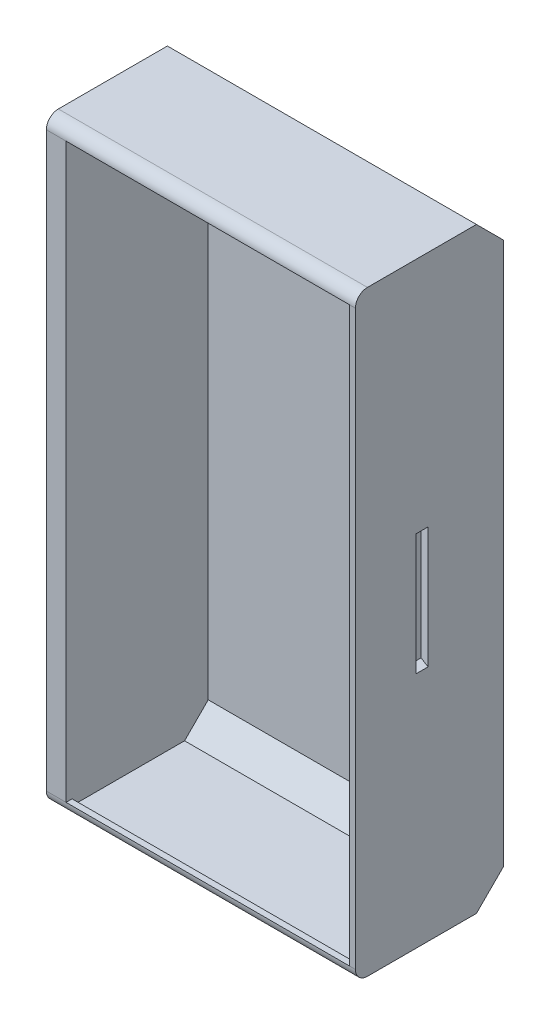
SolidWorks part; units mm, degrees
ref_plane "Front Plane" through (0, 0, 0) normal (1, 0, 0) x (0, 1, 0)
ref_plane "Top Plane" through (0, 0, 0) normal (0, 0, 1) x (0, 1, 0)
ref_plane "Right Plane" through (0, 0, 0) normal (0, 1, 0) x (-1, 0, 0)
sketch "Sketch1" plane through (0, 0, 0) normal (1, 0, 0) x (0, 1, 0)
  line L12 (-98.46, -46.9834) -> (-89.4834, -55.96)
  line L13 (-89.4834, -55.96) -> (89.4834, -55.96)
  line L14 (89.4834, -55.96) -> (98.46, -46.9834)
  line L15 (98.46, -46.9834) -> (98.46, -11)
  line L16 (94.5, -7.04) -> (-94.5, -7.04)
  line L17 (-98.46, -11) -> (-98.46, -46.9834)
  line L18 (-98.46, -46.9834) -> (-89.4834, -55.96)
  line L19 (-89.4834, -55.96) -> (89.4834, -55.96)
  line L20 (89.4834, -55.96) -> (98.46, -46.9834)
  line L21 (98.46, -46.9834) -> (98.46, -11)
  line L22 (94.5, -7.04) -> (-94.5, -7.04)
  line L23 (-98.46, -11) -> (-98.46, -46.9834)
  arc A4 (98.46, -11) -> (94.5, -7.04) centre (94.5, -11) ccw
  arc A5 (-94.5, -7.04) -> (-98.46, -11) centre (-94.5, -11) ccw
  arc A6 (98.46, -11) -> (94.5, -7.04) centre (94.5, -11) ccw
  arc A7 (-94.5, -7.04) -> (-98.46, -11) centre (-94.5, -11) ccw
  dimension "D1" = 0.04
extrude "Boss-Extrude1" add sketch "Sketch1" along normal up to surface (102 mm away) contours L18 L19 L20 L21 A6 L22 A7 L23
ref_plane "Plane3" through (0, 0, 0) normal (0, 1, 0) x (1, 0, 0)
sketch "Sketch11" plane through (0, 0, 0) normal (0, 1, 0) x (1, 0, 0)
  line L0 (102, 28.9917) -> (105.7243, 27.5325)
  line L1 (102, 11) -> (102, 46.9834) construction
  line L2 (102, 28.9917) -> (98.2757, 30.451)
  dimension "D1" = 4
  dimension "D2" = 4
sketch "Sketch12" plane through (102, 0, 0) normal (1, 0, 0) x (0, 1, 0)
  line L0 (0, -28.9917) -> (0, -27.5325) construction
  line L1 (-20, -30.9917) -> (20, -30.9917)
  line L2 (-20, -30.9917) -> (-20, -26.9917)
  line L3 (-20, -26.9917) -> (20, -26.9917)
  line L4 (20, -30.9917) -> (20, -26.9917)
  line L5 (-20, -30.9917) -> (20, -26.9917) construction
  line L6 (-20, -26.9917) -> (20, -30.9917) construction
  line L7 (0, -28.9917) -> (0, -30.451) construction
  point P0 (0, -28.9917)
  dimension "D1" = 40
  dimension "D2" = 4
sweep "Cut-Sweep1" cut profiles "Sketch12" path "Sketch11"
shell "Shell1" thickness 2 removed face at (51, 0, -7.04)
sketch "Sketch8" plane through (2, 0, 0) normal (1, 0, 0) x (0, 1, 0)
  line L11 (-10, -31.5) -> (-10, -21.5)
  line L12 (-10, -21.5) -> (10, -21.5)
  line L13 (10, -31.5) -> (10, -21.5)
  line L15 (-98.46, -46.9834) -> (-89.4834, -55.96)
  line L16 (-89.4834, -55.96) -> (89.4834, -55.96)
  line L17 (89.4834, -55.96) -> (98.46, -46.9834)
  line L18 (98.46, -46.9834) -> (98.46, -11)
  line L19 (94.5, -7.04) -> (-94.5, -7.04)
  line L20 (-98.46, -11) -> (-98.46, -46.9834)
  line L21 (-98.46, -46.9834) -> (-89.4834, -55.96)
  line L22 (-89.4834, -55.96) -> (89.4834, -55.96)
  line L23 (89.4834, -55.96) -> (98.46, -46.9834)
  line L24 (98.46, -46.9834) -> (98.46, -11)
  line L25 (94.5, -7.04) -> (-94.5, -7.04)
  line L26 (-98.46, -11) -> (-98.46, -46.9834)
  arc A0 (-10, -31.5) -> (10, -31.5) centre (0, -31.5) ccw
  arc A5 (98.46, -11) -> (94.5, -7.04) centre (94.5, -11) ccw
  arc A6 (-94.5, -7.04) -> (-98.46, -11) centre (-94.5, -11) ccw
  arc A7 (98.46, -11) -> (94.5, -7.04) centre (94.5, -11) ccw
  arc A8 (-94.5, -7.04) -> (-98.46, -11) centre (-94.5, -11) ccw
  point P4 (0, -55.96)
  dimension "D2" = 20
  dimension "D3" = 24.46
  dimension "D4" = 10
  dimension "D5" = 20
  dimension "D1" = 0
extrude "Boss-Extrude2" add sketch "Sketch8" along normal blind 2.5
sketch "Sketch10" plane through (4.5, 0, 0) normal (1, 0, 0) x (0, 1, 0)
  line L8 (94.5, -9.04) -> (94.5, -7.04)
  line L9 (94.5, -7.04) -> (-94.5, -7.04)
  line L10 (-94.5, -7.04) -> (-94.5, -9.04)
  line L11 (-96.46, -11) -> (-96.46, -46.155)
  line L12 (-96.46, -46.155) -> (-88.655, -53.96)
  line L13 (-88.655, -53.96) -> (88.655, -53.96)
  line L14 (88.655, -53.96) -> (96.46, -46.155)
  line L15 (96.46, -46.155) -> (96.46, -11)
  line L16 (94.5, -9.04) -> (94.5, -7.04)
  line L17 (94.5, -7.04) -> (-94.5, -7.04)
  line L18 (-94.5, -7.04) -> (-94.5, -9.04)
  line L19 (-96.46, -11) -> (-96.46, -46.155)
  line L20 (-96.46, -46.155) -> (-88.655, -53.96)
  line L21 (-88.655, -53.96) -> (88.655, -53.96)
  line L22 (88.655, -53.96) -> (96.46, -46.155)
  line L23 (96.46, -46.155) -> (96.46, -11)
  arc A2 (-94.5, -9.04) -> (-96.46, -11) centre (-94.5, -11) ccw
  arc A3 (96.46, -11) -> (94.5, -9.04) centre (94.5, -11) ccw
  arc A4 (-94.5, -9.04) -> (-96.46, -11) centre (-94.5, -11) ccw
  arc A5 (96.46, -11) -> (94.5, -9.04) centre (94.5, -11) ccw
  dimension "D1" = 0
extrude "Boss-Extrude3" add sketch "Sketch10" along normal blind 2
